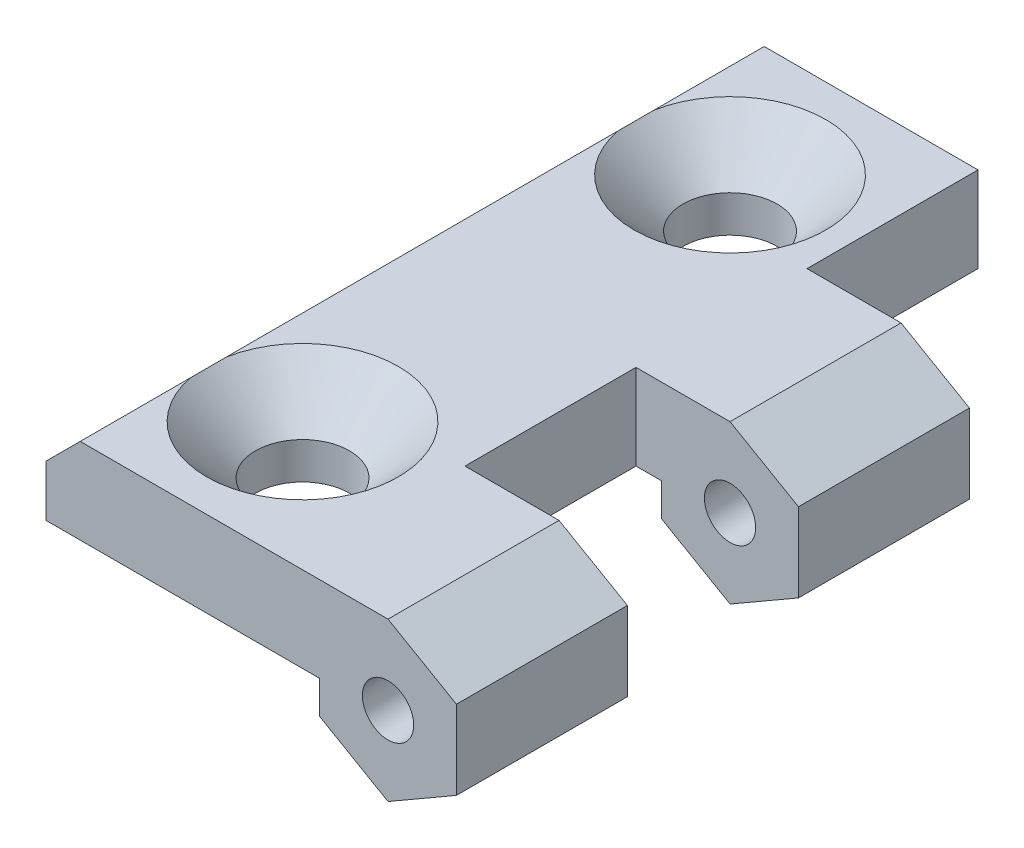
SolidWorks part; units mm, degrees
material "1060 合金"
ref_plane "前视基准面" through (0, 0, 0) normal (0, 0, 1) x (1, 0, 0)
ref_plane "上视基准面" through (0, 0, 0) normal (0, 1, 0) x (1, 0, 0)
ref_plane "右视基准面" through (0, 0, 0) normal (1, 0, 0) x (0, 0, -1)
sketch "草图1" plane through (0, 0, 0) normal (0, 0, 1) x (1, 0, 0)
  line L0 (10, 5) -> (-10, 5)
  line L1 (-10, 5) -> (-10, -1.9282)
  line L2 (-10, -1.9282) -> (6, -1.9282)
  line L3 (6, -1.9282) -> (10, -4.2376)
  line L4 (10, -4.2376) -> (14, -1.9282)
  line L5 (14, -1.9282) -> (14, 2.6906)
  line L6 (14, 2.6906) -> (10, 5)
extrude "凸台-拉伸1" add sketch "草图1" against normal blind 10
sketch "草图2" plane through (0, 0, 0) normal (0, 0, 1) x (1, 0, 0)
  line L0 (-10, 5) -> (6, 5)
  line L1 (6, 5) -> (6, -1.9282)
  line L2 (6, -1.9282) -> (-10, -1.9282)
  line L3 (-10, -1.9282) -> (-10, 5)
extrude "凸台-拉伸2" add sketch "草图2" along normal blind 10
sketch "草图3" plane through (6, 0, 0) normal (1, 0, 0) x (0, 0, -1)
  line L0 (-10, 5) -> (-10, -1.9282)
  line L1 (-10, -1.9282) -> (0, -1.9282)
  line L2 (0, -1.9282) -> (0, 5)
  line L3 (0, 5) -> (-10, 5)
extrude "切除-拉伸1" cut sketch "草图3" against normal blind 1.5
sketch "草图4" plane through (0, -1.9282, 0) normal (0, -1, 0) x (1, 0, 0)
  line L0 (4.5, 0) -> (4.5, 10)
  line L1 (4.5, 10) -> (-10, 10)
  line L2 (-10, 10) -> (-10, -10)
  line L3 (-10, -10) -> (6, -10)
  line L4 (6, -10) -> (6, 0)
  line L5 (6, 0) -> (4.5, 0)
extrude "切除-拉伸2" cut sketch "草图4" against normal blind 1.9282
sketch "草图5" plane through (0, 0, 10) normal (0, 0, 1) x (1, 0, 0)
  line L0 (-10, 5) -> (10, 5)
  line L1 (10, 5) -> (14, 2.6906)
  line L2 (14, 2.6906) -> (14, -1.9282)
  line L3 (14, -1.9282) -> (10, -4.2376)
  line L4 (10, -4.2376) -> (6, -1.9282)
  line L5 (6, -1.9282) -> (6, 0)
  line L6 (6, 0) -> (-10, 0)
  line L7 (-10, 0) -> (-10, 5)
extrude "凸台-拉伸3" add sketch "草图5" along normal blind 10
sketch "草图6" plane through (0, 0, -10) normal (0, 0, -1) x (-1, 0, 0)
  line L0 (-4.5, 0) -> (-4.5, 5)
  line L1 (-4.5, 5) -> (10, 5)
  line L2 (10, 5) -> (10, 0)
  line L3 (10, 0) -> (-4.5, 0)
extrude "凸台-拉伸4" add sketch "草图6" along normal blind 10
hole_wizard "Ø3.0 (3) 直径孔1" positions "草图8" profile "草图7" hole size "Ø3.0" standard "ANSI Metric"
sketch "草图8" plane through (0, 0, 10) normal (0, 0, -1) x (-1, 0, 0)
  point P0 (-10, 0.3812)
sketch "草图7" plane through (10, 0.3812, 10) normal (1, 0, 0) x (0, 1, 0)
  line L0 (0, 0) -> (0, 10)
  line L1 (0, 10) -> (1.5, 10)
  line L2 (1.5, 10) -> (1.5, 0)
  line L5 (1.5, 0) -> (0, 0)
  line L11 (0, -6.35) -> (0, 107.95) construction
  dimension "通孔孔直径" = 3
  dimension "通孔孔深度" = 10
hole_wizard "M5 平头机械螺钉的锥形沉头孔1" positions "草图10" profile "草图9" countersink size "M5" standard "ANSI Metric"
sketch "草图10" plane through (0, 5, 0) normal (0, 1, 0) x (1, 0, 0)
  point P0 (-2.5, 12.5)
  point P1 (-2.5, -12.5)
sketch "草图9" plane through (-2.5, 5, -12.5) normal (1, 0, 0) x (0, 0, 1)
  line L0 (0, 0) -> (0, 9.2376)
  line L1 (0, 9.2376) -> (2.75, 9.2376)
  line L2 (2.75, 9.2376) -> (2.75, 2.85)
  line L3 (2.75, 2.85) -> (5.6, 0)
  line L5 (5.6, 0) -> (0, 0)
  line L6 (-2.75, 2.85) -> (-5.6, 0) construction
  line L11 (0, -6.35) -> (0, 107.95) construction
  dimension "通孔孔直径" = 5.5
  dimension "通孔孔深度" = 9.2376
  dimension "近端锥形沉头孔直径" = 11.2
  dimension "近端锥形沉头孔角度" = 90
hole_wizard "Ø3.0 (3) 直径孔2" positions "草图12" profile "草图11" hole size "Ø3.0" standard "ANSI Metric"
sketch "草图12" plane through (0, 0, -10) normal (0, 0, -1) x (-1, 0, 0)
  point P0 (-10, 0.3812)
sketch "草图11" plane through (10, 0.3812, -10) normal (1, 0, 0) x (0, 1, 0)
  line L0 (0, 0) -> (0, 30)
  line L1 (0, 30) -> (1.5, 30)
  line L2 (1.5, 30) -> (1.5, 0)
  line L5 (1.5, 0) -> (0, 0)
  line L11 (0, -6.35) -> (0, 107.95) construction
  dimension "通孔孔直径" = 3
  dimension "通孔孔深度" = 30
chamfer "倒角1" distance 2 angle 45 1 edges at (-10, 5, 0)
